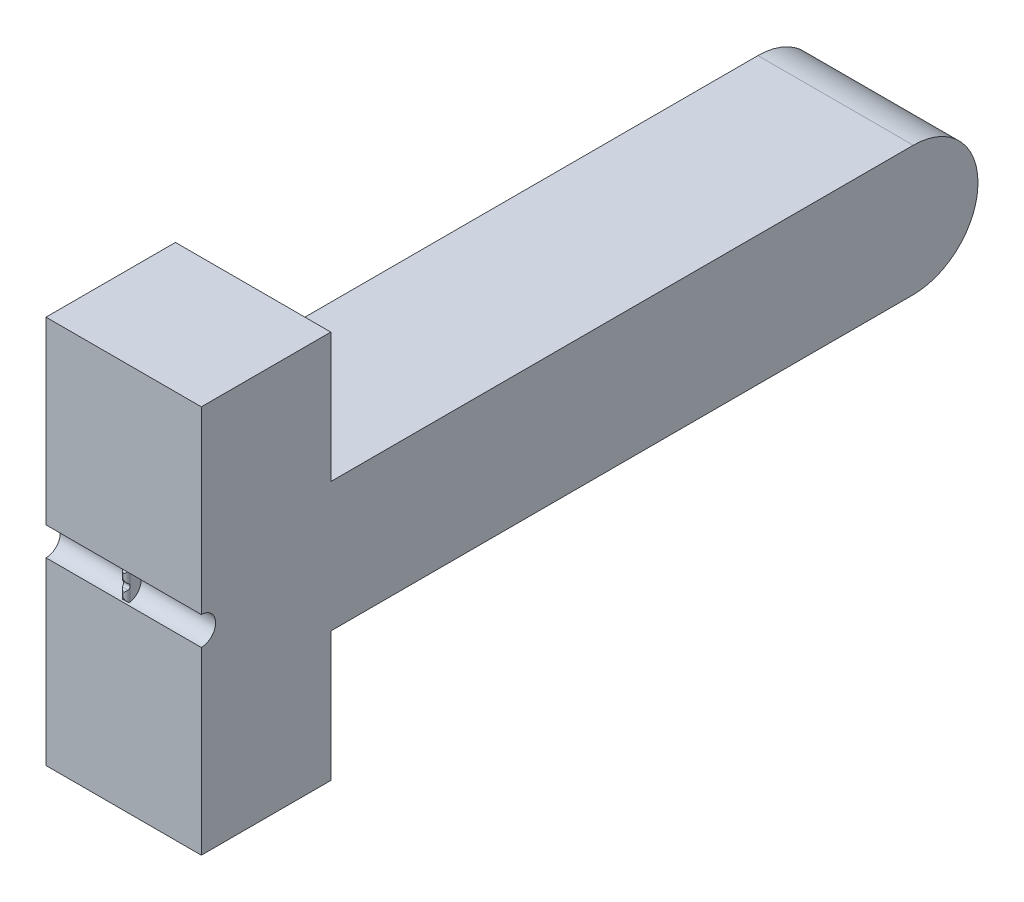
SolidWorks part; units mm, degrees
ref_plane "前视基准面" through (0, 0, 0) normal (0, 0, 1) x (1, 0, 0)
ref_plane "上视基准面" through (0, 0, 0) normal (0, 1, 0) x (1, 0, 0)
ref_plane "右视基准面" through (0, 0, 0) normal (1, 0, 0) x (0, 0, -1)
sketch "草图1" plane through (0, 0, 0) normal (0, 0, 1) x (1, 0, 0)
  line L1 (0, 0) -> (-12, 0)
  line L2 (0, 0) -> (0, 10)
  line L3 (0, 10) -> (-12, 10)
  line L4 (-12, 0) -> (-12, 10)
  dimension "D1" = 10
  dimension "D2" = 12
extrude "凸台-拉伸1" add sketch "草图1" along normal blind 60
sketch "草图2" plane through (-12, 0, 0) normal (-1, 0, 0) x (0, 0, 1)
  line L0 (60, 10) -> (0, 10) construction
  line L1 (0, 10) -> (0, 0) construction
  line L2 (5, 10) -> (0, 10)
  line L3 (0, 10) -> (0, 0)
  line L4 (0, 0) -> (5, 0)
  line L5 (60, 0) -> (0, 0) construction
  circle A0 centre (5, 5) radius 5
  line M1 (0, 10) -> (0, 0)
  line M2 (0, 0) -> (60, 0)
  line M4 (60, 10) -> (0, 10)
extrude "切除-拉伸3" cut sketch "草图2" against normal blind 60 contours A0 M4 M1 | A0 L3 M2 region at (-12, 8.8832, 1.1168) region at (-12, 1.1168, 1.1168)
sketch "草图3" plane through (-12, 0, 0) normal (-1, 0, 0) x (0, 0, 1)
  line L5 (60, 5) -> (60, 20)
  line L6 (60, 20) -> (50, 20)
  line L7 (50, -10) -> (60, -10)
  line L8 (50, 20) -> (50, -10)
  line L9 (60, -10) -> (60, 5)
  dimension "D1" = 15
  dimension "D2" = 10
  dimension "D3" = 10
  dimension "D4" = 30
extrude "凸台-拉伸2" add sketch "草图3" against normal blind 12
sketch "草图4" plane through (-12, 0, 0) normal (-1, 0, 0) x (0, 0, 1)
  line L0 (60, 20) -> (60, -10) construction
  circle A0 centre (60, 5) radius 1.1
  dimension "D1" = 2.2
extrude "切除-拉伸4" cut sketch "草图4" against normal blind 12
ref_plane "基准面1" through (-6, 0, 0) normal (1, 0, 0) x (0, 0, -1)
sketch "草图5" plane through (-6, 0, 0) normal (1, 0, 0) x (0, 0, -1)
  line L0 (-60, 6.1) -> (-60, 5.25)
  line L1 (-60, 3.9) -> (-60, 4.75)
  line L2 (-60, 5.25) -> (-60, 4.75)
  arc A0 (-60, 3.9) -> (-60, 6.1) centre (-60, 5) ccw
  arc A1 (-60, 3.9) -> (-60, 6.1) centre (-60, 5) ccw
  dimension "D1" = 2.2
extrude "凸台-拉伸3" add sketch "草图5" along normal mid plane 0.5 separate body contours L1 A0 L0 L2 region at (-6, 5, 59.5331)
sketch "草图6" plane through (-6, 0, 0) normal (1, 0, 0) x (0, 0, -1)
  line L0 (-60, 3.9) -> (-60, 6.1) construction
  circle A0 centre (-60, 5) radius 0.25
  dimension "D1" = 0.5
extrude "切除-拉伸5" cut sketch "草图6" against normal mid plane 3
fillet "圆角1" radius 0.25 8 edges at (-6.25, 5.675, 60) (-6, 6.1, 60) (-5.75, 5.675, 60) (-6, 5.25, 60) (-5.75, 4.325, 60) (-6, 3.9, 60) (-6.25, 4.325, 60) (-6, 4.75, 60)
